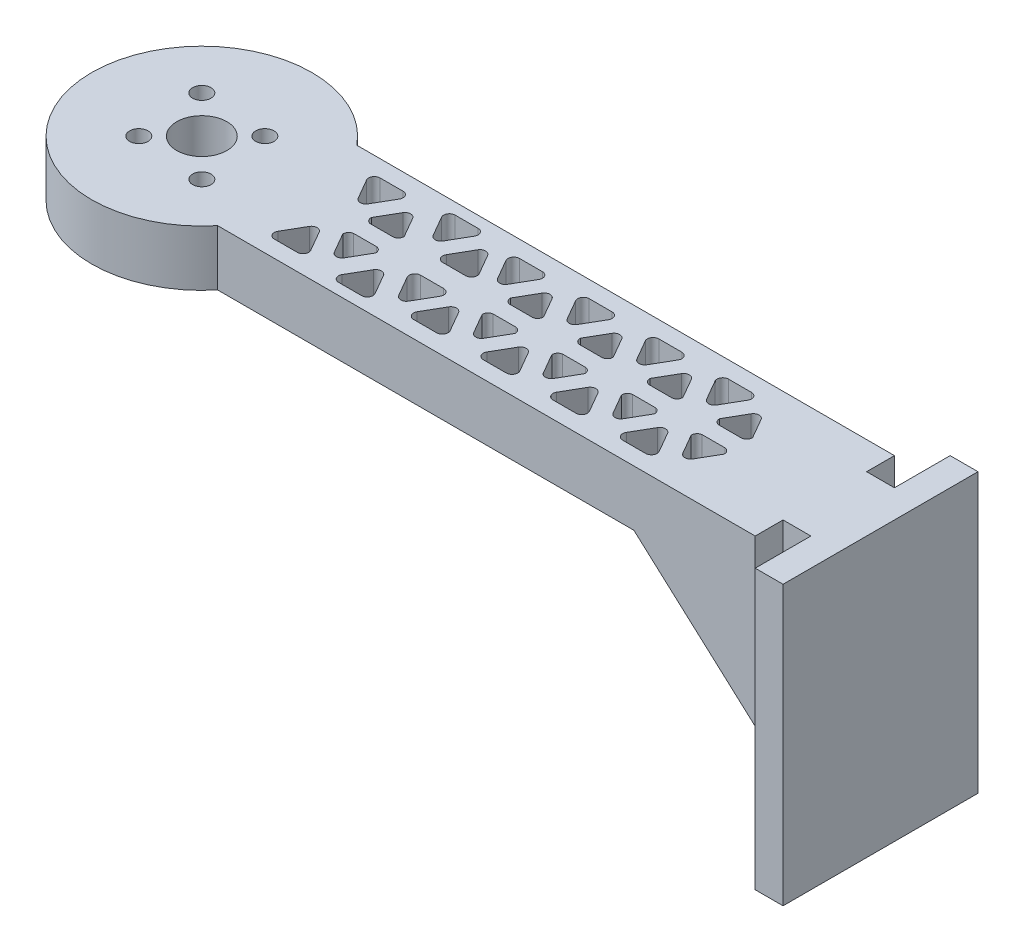
SolidWorks part; units mm, degrees
note: The reader was unsure of these and kept them because the rebuilt part matched: shared geometry of "Sketch2<3>".
ref_plane "Front Plane" through (0, 0, 0) normal (0, 0, 1) x (1, 0, 0)
ref_plane "Top Plane" through (0, 0, 0) normal (0, 1, 0) x (1, 0, 0)
ref_plane "Right Plane" through (0, 0, 0) normal (1, 0, 0) x (0, 0, -1)
sketch "Sketch1" plane through (0, 0, 0) normal (0, 1, 0) x (1, 0, 0)
  line L0 (19.7818, 0) -> (121.8484, 0) construction
  line L1 (15.332, 12.5) -> (121.8484, 12.5)
  line L2 (15.332, -12.5) -> (121.8484, -12.5)
  line L3 (121.8484, 12.5) -> (121.8484, -12.5)
  line L4 (22.5013, 9.5) -> (26.6358, 9.5)
  line L5 (27.5225, 7.9638) -> (25.4552, 4.3855)
  line L6 (23.682, 4.3855) -> (21.6147, 7.9638)
  line L7 (29.935, 6.1427) -> (27.8677, 2.5644)
  line L8 (33.7755, 2.5565) -> (31.7082, 6.1427)
  line L9 (28.7543, 1.5) -> (32.8889, 1.5)
  line L21 (37.9612, 5.3448) -> (40.0285, 8.9231)
  line L22 (34.1207, 8.9231) -> (36.188, 5.3448)
  line L23 (39.1419, 10.4593) -> (35.0073, 10.4593)
  line L26 (45.3949, 1.9796) -> (41.2604, 1.9796)
  line L27 (40.3733, 3.5149) -> (42.441, 7.1019)
  line L28 (44.2142, 7.1019) -> (46.2815, 3.5236)
  line L29 (35.0113, 9.5) -> (39.1458, 9.5) [skipped]
  line L30 (40.0325, 7.9638) -> (37.9652, 4.3855) [skipped]
  line L31 (36.192, 4.3855) -> (34.1247, 7.9638) [skipped]
  line L32 (42.445, 6.1427) -> (40.3777, 2.5644) [skipped]
  line L33 (46.2855, 2.5565) -> (44.2182, 6.1427) [skipped]
  line L34 (41.2643, 1.5) -> (45.3989, 1.5) [skipped]
  line L35 (47.5213, 9.5) -> (51.6558, 9.5)
  line L36 (52.5425, 7.9638) -> (50.4752, 4.3855)
  line L37 (48.702, 4.3855) -> (46.6347, 7.9638)
  line L38 (54.955, 6.1427) -> (52.8877, 2.5644)
  line L39 (58.7955, 2.5565) -> (56.7282, 6.1427)
  line L40 (53.7743, 1.5) -> (57.9089, 1.5)
  line L41 (60.0313, 9.5) -> (64.1658, 9.5)
  line L42 (65.0525, 7.9638) -> (62.9852, 4.3855)
  line L43 (61.212, 4.3855) -> (59.1447, 7.9638)
  line L44 (67.465, 6.1427) -> (65.3977, 2.5644)
  line L45 (71.3055, 2.5565) -> (69.2382, 6.1427)
  line L46 (66.2843, 1.5) -> (70.4189, 1.5)
  line L47 (72.5413, 9.5) -> (76.6758, 9.5)
  line L48 (77.5625, 7.9638) -> (75.4952, 4.3855)
  line L49 (73.722, 4.3855) -> (71.6547, 7.9638)
  line L50 (79.975, 6.1427) -> (77.9077, 2.5644)
  line L51 (83.8155, 2.5565) -> (81.7482, 6.1427)
  line L52 (78.7943, 1.5) -> (82.9289, 1.5)
  line L53 (85.0513, 9.5) -> (89.1858, 9.5)
  line L54 (90.0725, 7.9638) -> (88.0052, 4.3855)
  line L55 (86.232, 4.3855) -> (84.1647, 7.9638)
  line L56 (92.485, 6.1427) -> (90.4177, 2.5644)
  line L57 (96.3255, 2.5565) -> (94.2582, 6.1427)
  line L58 (91.3043, 1.5) -> (95.4389, 1.5)
  line L59 (91.3043, -1.5) -> (95.4389, -1.5)
  line L60 (96.3255, -2.5565) -> (94.2582, -6.1427)
  line L61 (92.485, -6.1427) -> (90.4177, -2.5644)
  line L62 (86.232, -4.3855) -> (84.1647, -7.9638)
  line L63 (90.0725, -7.9638) -> (88.0052, -4.3855)
  line L64 (85.0513, -9.5) -> (89.1858, -9.5)
  line L65 (78.7943, -1.5) -> (82.9289, -1.5)
  line L66 (83.8155, -2.5565) -> (81.7482, -6.1427)
  line L67 (79.975, -6.1427) -> (77.9077, -2.5644)
  line L68 (73.722, -4.3855) -> (71.6547, -7.9638)
  line L69 (77.5625, -7.9638) -> (75.4952, -4.3855)
  line L70 (72.5413, -9.5) -> (76.6758, -9.5)
  line L71 (66.2843, -1.5) -> (70.4189, -1.5)
  line L72 (71.3055, -2.5565) -> (69.2382, -6.1427)
  line L73 (67.465, -6.1427) -> (65.3977, -2.5644)
  line L74 (61.212, -4.3855) -> (59.1447, -7.9638)
  line L75 (65.0525, -7.9638) -> (62.9852, -4.3855)
  line L76 (60.0313, -9.5) -> (64.1658, -9.5)
  line L77 (53.7743, -1.5) -> (57.9089, -1.5)
  line L78 (58.7955, -2.5565) -> (56.7282, -6.1427)
  line L79 (54.955, -6.1427) -> (52.8877, -2.5644)
  line L80 (48.702, -4.3855) -> (46.6347, -7.9638)
  line L81 (52.5425, -7.9638) -> (50.4752, -4.3855)
  line L82 (47.5213, -9.5) -> (51.6558, -9.5)
  line L83 (44.2142, -7.1019) -> (46.2815, -3.5236)
  line L84 (40.3733, -3.5149) -> (42.441, -7.1019)
  line L85 (45.3949, -1.9796) -> (41.2604, -1.9796)
  line L86 (39.1419, -10.4593) -> (35.0073, -10.4593)
  line L87 (34.1207, -8.9231) -> (36.188, -5.3448)
  line L88 (37.9612, -5.3448) -> (40.0285, -8.9231)
  line L89 (28.7543, -1.5) -> (32.8889, -1.5)
  line L90 (33.7755, -2.5565) -> (31.7082, -6.1427)
  line L91 (29.935, -6.1427) -> (27.8677, -2.5644)
  line L92 (23.682, -4.3855) -> (21.6147, -7.9638)
  line L93 (27.5225, -7.9638) -> (25.4552, -4.3855)
  line L94 (22.5013, -9.5) -> (26.6358, -9.5)
  line L95 (0, -16.7095) -> (0, 16.7095) construction
  line L97 (11.8116, -11.8116) -> (-11.8116, 11.8116) construction
  line L100 (-12.5321, -12.5321) -> (12.5321, 12.5321) construction
  circle A0 centre (0, 0) radius 19.7818
  arc A5 (25.4552, 4.3855) -> (23.682, 4.3855) centre (24.5686, 4.8978) cw
  arc A6 (22.5013, 9.5) -> (21.6147, 7.9638) centre (22.5013, 8.4761) ccw
  arc A7 (26.6358, 9.5) -> (27.5225, 7.9638) centre (26.6358, 8.4761) cw
  arc A8 (32.8889, 1.5) -> (33.7755, 2.5565) centre (32.7524, 2.5148) ccw
  arc A9 (31.7082, 6.1427) -> (29.935, 6.1427) centre (30.8216, 5.6305) ccw
  arc A10 (28.7543, 1.5) -> (27.8677, 2.5644) centre (28.8905, 2.5148) cw
  arc A20 (35.0073, 10.4593) -> (34.1207, 8.9231) centre (35.0073, 9.4353) ccw
  arc A21 (39.1419, 10.4593) -> (40.0285, 8.9231) centre (39.1419, 9.4353) cw
  arc A22 (36.188, 5.3448) -> (37.9612, 5.3448) centre (37.0746, 5.857) ccw
  arc A23 (45.3949, 1.9796) -> (46.2815, 3.5236) centre (45.3995, 3.0036) ccw
  arc A24 (42.441, 7.1019) -> (44.2142, 7.1019) centre (43.3276, 6.5897) cw
  arc A25 (41.2604, 1.9796) -> (40.3733, 3.5149) centre (41.2604, 3.0036) cw
  arc A26 (37.9652, 4.3855) -> (36.192, 4.3855) centre (37.0786, 4.8978) cw [skipped]
  arc A27 (35.0113, 9.5) -> (34.1247, 7.9638) centre (35.0113, 8.4761) ccw [skipped]
  arc A28 (39.1458, 9.5) -> (40.0325, 7.9638) centre (39.1458, 8.4761) cw [skipped]
  arc A29 (45.3989, 1.5) -> (46.2855, 2.5565) centre (45.2624, 2.5148) ccw [skipped]
  arc A30 (44.2182, 6.1427) -> (42.445, 6.1427) centre (43.3316, 5.6305) ccw [skipped]
  arc A31 (41.2643, 1.5) -> (40.3777, 2.5644) centre (41.4005, 2.5148) cw [skipped]
  arc A32 (50.4752, 4.3855) -> (48.702, 4.3855) centre (49.5886, 4.8978) cw
  arc A33 (47.5213, 9.5) -> (46.6347, 7.9638) centre (47.5213, 8.4761) ccw
  arc A34 (51.6558, 9.5) -> (52.5425, 7.9638) centre (51.6558, 8.4761) cw
  arc A35 (57.9089, 1.5) -> (58.7955, 2.5565) centre (57.7724, 2.5148) ccw
  arc A36 (56.7282, 6.1427) -> (54.955, 6.1427) centre (55.8416, 5.6305) ccw
  arc A37 (53.7743, 1.5) -> (52.8877, 2.5644) centre (53.9105, 2.5148) cw
  arc A38 (62.9852, 4.3855) -> (61.212, 4.3855) centre (62.0986, 4.8978) cw
  arc A39 (60.0313, 9.5) -> (59.1447, 7.9638) centre (60.0313, 8.4761) ccw
  arc A40 (64.1658, 9.5) -> (65.0525, 7.9638) centre (64.1658, 8.4761) cw
  arc A41 (70.4189, 1.5) -> (71.3055, 2.5565) centre (70.2824, 2.5148) ccw
  arc A42 (69.2382, 6.1427) -> (67.465, 6.1427) centre (68.3516, 5.6305) ccw
  arc A43 (66.2843, 1.5) -> (65.3977, 2.5644) centre (66.4205, 2.5148) cw
  arc A44 (75.4952, 4.3855) -> (73.722, 4.3855) centre (74.6086, 4.8978) cw
  arc A45 (72.5413, 9.5) -> (71.6547, 7.9638) centre (72.5413, 8.4761) ccw
  arc A46 (76.6758, 9.5) -> (77.5625, 7.9638) centre (76.6758, 8.4761) cw
  arc A47 (82.9289, 1.5) -> (83.8155, 2.5565) centre (82.7924, 2.5148) ccw
  arc A48 (81.7482, 6.1427) -> (79.975, 6.1427) centre (80.8616, 5.6305) ccw
  arc A49 (78.7943, 1.5) -> (77.9077, 2.5644) centre (78.9305, 2.5148) cw
  arc A50 (88.0052, 4.3855) -> (86.232, 4.3855) centre (87.1186, 4.8978) cw
  arc A51 (85.0513, 9.5) -> (84.1647, 7.9638) centre (85.0513, 8.4761) ccw
  arc A52 (89.1858, 9.5) -> (90.0725, 7.9638) centre (89.1858, 8.4761) cw
  arc A53 (95.4389, 1.5) -> (96.3255, 2.5565) centre (95.3024, 2.5148) ccw
  arc A54 (94.2582, 6.1427) -> (92.485, 6.1427) centre (93.3716, 5.6305) ccw
  arc A55 (91.3043, 1.5) -> (90.4177, 2.5644) centre (91.4405, 2.5148) cw
  arc A56 (91.3043, -1.5) -> (90.4177, -2.5644) centre (91.4405, -2.5148) ccw
  arc A57 (94.2582, -6.1427) -> (92.485, -6.1427) centre (93.3716, -5.6305) cw
  arc A58 (95.4389, -1.5) -> (96.3255, -2.5565) centre (95.3024, -2.5148) cw
  arc A59 (89.1858, -9.5) -> (90.0725, -7.9638) centre (89.1858, -8.4761) ccw
  arc A60 (85.0513, -9.5) -> (84.1647, -7.9638) centre (85.0513, -8.4761) cw
  arc A61 (88.0052, -4.3855) -> (86.232, -4.3855) centre (87.1186, -4.8978) ccw
  arc A62 (78.7943, -1.5) -> (77.9077, -2.5644) centre (78.9305, -2.5148) ccw
  arc A63 (81.7482, -6.1427) -> (79.975, -6.1427) centre (80.8616, -5.6305) cw
  arc A64 (82.9289, -1.5) -> (83.8155, -2.5565) centre (82.7924, -2.5148) cw
  arc A65 (76.6758, -9.5) -> (77.5625, -7.9638) centre (76.6758, -8.4761) ccw
  arc A66 (72.5413, -9.5) -> (71.6547, -7.9638) centre (72.5413, -8.4761) cw
  arc A67 (75.4952, -4.3855) -> (73.722, -4.3855) centre (74.6086, -4.8978) ccw
  arc A68 (66.2843, -1.5) -> (65.3977, -2.5644) centre (66.4205, -2.5148) ccw
  arc A69 (69.2382, -6.1427) -> (67.465, -6.1427) centre (68.3516, -5.6305) cw
  arc A70 (70.4189, -1.5) -> (71.3055, -2.5565) centre (70.2824, -2.5148) cw
  arc A71 (64.1658, -9.5) -> (65.0525, -7.9638) centre (64.1658, -8.4761) ccw
  arc A72 (60.0313, -9.5) -> (59.1447, -7.9638) centre (60.0313, -8.4761) cw
  arc A73 (62.9852, -4.3855) -> (61.212, -4.3855) centre (62.0986, -4.8978) ccw
  arc A74 (53.7743, -1.5) -> (52.8877, -2.5644) centre (53.9105, -2.5148) ccw
  arc A75 (56.7282, -6.1427) -> (54.955, -6.1427) centre (55.8416, -5.6305) cw
  arc A76 (57.9089, -1.5) -> (58.7955, -2.5565) centre (57.7724, -2.5148) cw
  arc A77 (51.6558, -9.5) -> (52.5425, -7.9638) centre (51.6558, -8.4761) ccw
  arc A78 (47.5213, -9.5) -> (46.6347, -7.9638) centre (47.5213, -8.4761) cw
  arc A79 (50.4752, -4.3855) -> (48.702, -4.3855) centre (49.5886, -4.8978) ccw
  arc A80 (41.2604, -1.9796) -> (40.3733, -3.5149) centre (41.2604, -3.0036) ccw
  arc A81 (42.441, -7.1019) -> (44.2142, -7.1019) centre (43.3276, -6.5897) ccw
  arc A82 (45.3949, -1.9796) -> (46.2815, -3.5236) centre (45.3995, -3.0036) cw
  arc A83 (36.188, -5.3448) -> (37.9612, -5.3448) centre (37.0746, -5.857) cw
  arc A84 (39.1419, -10.4593) -> (40.0285, -8.9231) centre (39.1419, -9.4353) ccw
  arc A85 (35.0073, -10.4593) -> (34.1207, -8.9231) centre (35.0073, -9.4353) cw
  arc A86 (28.7543, -1.5) -> (27.8677, -2.5644) centre (28.8905, -2.5148) ccw
  arc A87 (31.7082, -6.1427) -> (29.935, -6.1427) centre (30.8216, -5.6305) cw
  arc A88 (32.8889, -1.5) -> (33.7755, -2.5565) centre (32.7524, -2.5148) cw
  arc A89 (26.6358, -9.5) -> (27.5225, -7.9638) centre (26.6358, -8.4761) ccw
  arc A90 (22.5013, -9.5) -> (21.6147, -7.9638) centre (22.5013, -8.4761) cw
  arc A91 (25.4552, -4.3855) -> (23.682, -4.3855) centre (24.5686, -4.8978) ccw
  circle A92 centre (-6.7175, 6.7175) radius 1.65
  circle A93 centre (5.6569, 5.6569) radius 1.65
  circle A94 centre (6.7175, -6.7175) radius 1.65
  circle A95 centre (-5.6569, -5.6569) radius 1.65
  circle A96 centre (0, 0) radius 4.5
  point P5 (0, 0)
  point P8 (0, 0)
  point P55 (30.8216, 5.6305)
  point P68 (37.0746, 5.857)
  point P76 (43.3276, 6.5897)
  point P93 (43.3316, 5.6305)
  point P112 (55.8416, 5.6305)
  point P131 (68.3516, 5.6305)
  point P150 (80.8616, 5.6305)
  point P169 (93.3716, 5.6305)
  point P258 (93.3716, -5.6305)
  point P259 (80.8616, -5.6305)
  point P260 (68.3516, -5.6305)
  point P261 (55.8416, -5.6305)
  point P262 (43.3276, -6.5897)
  point P263 (37.0746, -5.857)
  point P264 (30.8216, -5.6305)
  point P266 (0, 0)
  dimension "D6" = 45
  dimension "D7" = 90
  dimension "D8" = 3.3
  dimension "D9" = 3.3
  dimension "D10" = 3.3
  dimension "D11" = 3.3
  dimension "D16" = 9
  dimension "D1" = 3
  dimension "D2" = 3
  dimension "D3" = 25
  dimension "D5" = 3
  dimension "D12" = 9.5
  dimension "D13" = 9.5
  dimension "D14" = 8
  dimension "D15" = 8
  dimension "D4" = 6
extrude "Boss-Extrude2" add sketch "Sketch1" along normal blind 10
sketch "Sketch2" plane through (0, 10, 0) normal (0, 1, 0) x (1, 0, 0)
  line L0 (121.8484, 12.5) -> (121.8484, 17.5)
  line L2 (121.8484, 17.5) -> (116.8484, 17.5)
  line L3 (116.8484, 17.5) -> (116.8484, 12.5)
  line L4 (15.332, 12.5) -> (121.8484, 12.5) construction
  line L6 (121.8484, 0) -> (109.1771, 0) construction
  line L7 (121.8484, 12.5) -> (121.8484, -12.5) construction
  line L9 (116.8484, -17.5) -> (116.8484, -12.5)
  line L10 (121.8484, -17.5) -> (116.8484, -17.5)
  line L11 (121.8484, -12.5) -> (121.8484, -17.5)
  line L12 (116.8484, 12.5) -> (116.8484, -12.5)
  line L13 (121.8484, 12.5) -> (121.8484, -12.5)
  line L14 (116.8484, 12.5) -> (111.8484, 12.5)
  line L15 (111.8484, 12.5) -> (111.8484, 7.5)
  line L16 (111.8484, 7.5) -> (116.8484, 7.5)
  line L17 (116.8484, -12.5) -> (111.8484, -12.5)
  line L18 (111.8484, -7.5) -> (116.8484, -7.5)
  line L19 (111.8484, -12.5) -> (111.8484, -7.5)
  line L20 (116.8484, 12.5) -> (116.8484, 7.5)
  line L21 (116.8484, -7.5) -> (116.8484, -12.5)
  dimension "D1" = 5
  dimension "D2" = 5
  dimension "D3" = 5
  dimension "D4" = 5
extrude "Boss-Extrude3" add sketch "Sketch2" against normal blind 50 contours L2 L3 L12 L9 L10 L11 L13 L0
sketch "Sketch3" plane through (0, 0, 12.5) normal (0, 0, 1) x (1, 0, 0)
  line L0 (90.0725, 0) -> (116.8484, -24.0811)
  line L1 (116.8484, -40) -> (116.8484, 10) construction
  line L2 (90.0725, 0) -> (116.8484, 0)
  line L3 (15.332, 0) -> (116.8484, 0) construction
  line L4 (116.8484, 0) -> (116.8484, -24.0811)
extrude "Boss-Extrude4" add sketch "Sketch3" against normal up to surface (25 mm away) contours L0 L4 L2 up to face at (66.0902, 5, -12.5)
extrude "Cut-Extrude1" cut sketch "Sketch2<3>" against normal up to vertex contours L15 L16 L12 L14 | L19 L17 L12 L18
sketch "Sketch2<3>" plane through (0, 10, 0) normal (0, 1, 0) x (1, 0, 0) same geometry as "Sketch2"
